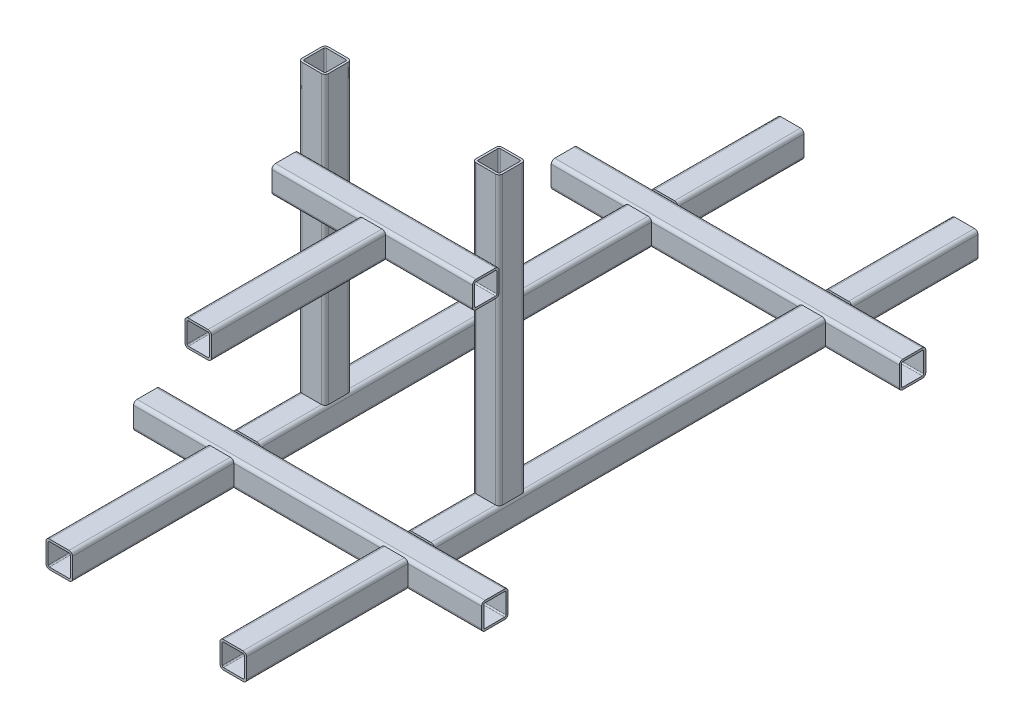
SolidWorks part; units mm, degrees
material "Alumina"
ref_plane "Front Plane" through (0, 0, 0) normal (0, 0, 1) x (1, 0, 0)
ref_plane "Top Plane" through (0, 0, 0) normal (0, 1, 0) x (1, 0, 0)
ref_plane "Right Plane" through (0, 0, 0) normal (1, 0, 0) x (0, 0, -1)
ref_plane "Bottom Face" through (0, 0, 0) normal (0, 1, 0) x (1, 0, 0)
ref_plane "Top Face" through (0, 38.1, 0) normal (0, 1, 0) x (1, 0, 0)
ref_plane "Mid Plane" through (0, 19.05, 0) normal (0, 1, 0) x (1, 0, 0)
ref_plane "Front Face" through (0, 0, 500) normal (0, 0, 1) x (1, 0, 0)
ref_plane "Back Face" through (0, 0, -500) normal (0, 0, 1) x (1, 0, 0)
ref_plane "Left Face" through (250, 0, 0) normal (1, 0, 0) x (0, 0, -1)
ref_plane "Right Face" through (-250, 0, 0) normal (1, 0, 0) x (0, 0, -1)
ref_plane "Divider Plane" through (0, 0, 150) normal (0, 0, 1) x (1, 0, 0)
ref_plane "Max Height Plane" through (0, 450, 0) normal (0, 1, 0) x (1, 0, 0)
ref_plane "Electronics Box Plane" through (0, 338.1, 0) normal (0, 1, 0) x (1, 0, 0)
sketch "Sketch2" plane through (250, 0, 0) normal (1, 0, 0) x (0, 0, -1)
  line L0 (330, 38.1) -> (-330, 38.1) construction
  line L5 (330, 0) -> (-330, 0) construction
  line L6 (0, 220) -> (0, -220) construction
  line L7 (-314.05, 38.1) -> (-285.95, 38.1)
  line L8 (-280.95, 33.1) -> (-280.95, 5)
  line L9 (-315.875, 33.1) -> (-315.875, 5)
  line L10 (-314.05, 3.175) -> (-285.95, 3.175)
  line L11 (-285.95, 0) -> (-314.05, 0)
  line L12 (-319.05, 5) -> (-319.05, 33.1)
  line L13 (-300, 38.1) -> (-300, 0) construction
  line L14 (-319.05, 19.05) -> (-280.95, 19.05) construction
  line L15 (-284.125, 5) -> (-284.125, 33.1)
  line L16 (-285.95, 34.925) -> (-314.05, 34.925)
  line L17 (-300, 34.925) -> (-300, 3.175) construction
  line L18 (-315.875, 19.05) -> (-284.125, 19.05) construction
  arc A0 (-285.95, 38.1) -> (-280.95, 33.1) centre (-285.95, 33.1) cw
  arc A1 (-280.95, 5) -> (-285.95, 0) centre (-285.95, 5) cw
  arc A2 (-314.05, 0) -> (-319.05, 5) centre (-314.05, 5) cw
  arc A3 (-319.05, 33.1) -> (-314.05, 38.1) centre (-314.05, 33.1) cw
  arc A4 (-315.875, 5) -> (-314.05, 3.175) centre (-314.05, 5) ccw
  arc A5 (-285.95, 3.175) -> (-284.125, 5) centre (-285.95, 5) ccw
  arc A6 (-284.125, 33.1) -> (-285.95, 34.925) centre (-285.95, 33.1) ccw
  arc A7 (-314.05, 34.925) -> (-315.875, 33.1) centre (-314.05, 33.1) ccw
  point P20 (-300, 19.05)
  point P39 (-300, 19.05)
  dimension "D1" = 5
  dimension "D2" = 300
  dimension "D3" = 3.175
extrude "Front Cross-Car Member" add sketch "Sketch2" against normal up to surface (500 mm away) up to plane "Right Face"
sketch "Sketch5" plane through (250, 0, 0) normal (1, 0, 0) x (0, 0, -1)
  line L0 (285.95, 38.1) -> (314.05, 38.1)
  line L1 (319.05, 33.1) -> (319.05, 5)
  line L2 (314.05, 0) -> (285.95, 0)
  line L3 (280.95, 5) -> (280.95, 33.1)
  line L4 (300, 38.1) -> (300, 0) construction
  line L5 (280.95, 19.05) -> (319.05, 19.05) construction
  line L6 (285.95, 34.925) -> (314.05, 34.925)
  line L7 (315.875, 33.1) -> (315.875, 5)
  line L8 (314.05, 3.175) -> (285.95, 3.175)
  line L9 (284.125, 5) -> (284.125, 33.1)
  line L10 (300, 34.925) -> (300, 3.175) construction
  line L11 (284.125, 19.05) -> (315.875, 19.05) construction
  line L12 (330, 0) -> (-330, 0) construction
  line L14 (330, 38.1) -> (-330, 38.1) construction
  line L15 (0, 220) -> (0, -220) construction
  arc A0 (314.05, 38.1) -> (319.05, 33.1) centre (314.05, 33.1) cw
  arc A1 (319.05, 5) -> (314.05, 0) centre (314.05, 5) cw
  arc A2 (285.95, 0) -> (280.95, 5) centre (285.95, 5) cw
  arc A3 (280.95, 33.1) -> (285.95, 38.1) centre (285.95, 33.1) cw
  arc A4 (314.05, 34.925) -> (315.875, 33.1) centre (314.05, 33.1) cw
  arc A5 (315.875, 5) -> (314.05, 3.175) centre (314.05, 5) cw
  arc A6 (285.95, 3.175) -> (284.125, 5) centre (285.95, 5) cw
  arc A7 (284.125, 33.1) -> (285.95, 34.925) centre (285.95, 33.1) cw
  point P32 (300, 19.05)
  point P33 (300, 19.05)
  dimension "D2" = 5
  dimension "D1" = 3.175
  dimension "D3" = 300
extrude "Back Cross-Car Member" add sketch "Sketch5" against normal up to surface (500 mm away) separate body up to plane "Right Face"
sketch "Sketch6" plane through (0, 0, -500) normal (0, 0, 1) x (1, 0, 0)
  line L0 (110.95, 38.1) -> (139.05, 38.1)
  line L1 (144.05, 33.1) -> (144.05, 5)
  line L2 (109.125, 33.1) -> (109.125, 5)
  line L3 (110.95, 3.175) -> (139.05, 3.175)
  line L4 (139.05, 0) -> (110.95, 0)
  line L5 (105.95, 5) -> (105.95, 33.1)
  line L6 (125, 38.1) -> (125, 0) construction
  line L7 (105.95, 19.05) -> (144.05, 19.05) construction
  line L8 (140.875, 5) -> (140.875, 33.1)
  line L9 (139.05, 34.925) -> (110.95, 34.925)
  line L10 (125, 34.925) -> (125, 3.175) construction
  line L11 (109.125, 19.05) -> (140.875, 19.05) construction
  line L12 (330, 38.1) -> (-330, 38.1) construction
  line L13 (330, 0) -> (-330, 0) construction
  line L14 (0, -220) -> (0, 220) construction
  arc A0 (139.05, 38.1) -> (144.05, 33.1) centre (139.05, 33.1) cw
  arc A1 (144.05, 5) -> (139.05, 0) centre (139.05, 5) cw
  arc A2 (110.95, 0) -> (105.95, 5) centre (110.95, 5) cw
  arc A3 (105.95, 33.1) -> (110.95, 38.1) centre (110.95, 33.1) cw
  arc A4 (109.125, 5) -> (110.95, 3.175) centre (110.95, 5) ccw
  arc A5 (139.05, 3.175) -> (140.875, 5) centre (139.05, 5) ccw
  arc A6 (140.875, 33.1) -> (139.05, 34.925) centre (139.05, 33.1) ccw
  arc A7 (110.95, 34.925) -> (109.125, 33.1) centre (110.95, 33.1) ccw
  point P16 (125, 19.05)
  point P33 (125, 19.05)
  dimension "D1" = 5
  dimension "D2" = 3.175
  dimension "D3" = 125
extrude "Back Left Along-Car Member" add sketch "Sketch6" along normal blind 180.95
extrude "Middle Left Along-Car Member" add sketch "Sketch6<2>" along normal blind 561.9 from offset 219.05
sketch "Sketch6<2>" plane through (0, 0, -500) normal (0, 0, 1) x (1, 0, 0) same geometry as "Sketch6"
extrude "Front Left Along-Car Member" add sketch "Sketch6<3>" along normal blind 231.75 from offset 819.05
sketch "Sketch6<3>" plane through (0, 0, -500) normal (0, 0, 1) x (1, 0, 0) same geometry as "Sketch6"
sketch "Sketch7" plane through (0, 0, -500) normal (0, 0, 1) x (1, 0, 0)
  line L0 (-139.05, 38.1) -> (-110.95, 38.1)
  line L1 (-105.95, 33.1) -> (-105.95, 5)
  line L2 (-140.875, 33.1) -> (-140.875, 5)
  line L3 (-139.05, 3.175) -> (-110.95, 3.175)
  line L4 (-110.95, 0) -> (-139.05, 0)
  line L5 (-144.05, 5) -> (-144.05, 33.1)
  line L6 (-125, 38.1) -> (-125, 0) construction
  line L7 (-144.05, 19.05) -> (-105.95, 19.05) construction
  line L8 (-109.125, 5) -> (-109.125, 33.1)
  line L9 (-110.95, 34.925) -> (-139.05, 34.925)
  line L10 (-125, 34.925) -> (-125, 3.175) construction
  line L11 (-140.875, 19.05) -> (-109.125, 19.05) construction
  line L12 (330, 38.1) -> (-330, 38.1) construction
  line L13 (330, 0) -> (-330, 0) construction
  line L14 (0, -220) -> (0, 220) construction
  arc A0 (-110.95, 38.1) -> (-105.95, 33.1) centre (-110.95, 33.1) cw
  arc A1 (-105.95, 5) -> (-110.95, 0) centre (-110.95, 5) cw
  arc A2 (-139.05, 0) -> (-144.05, 5) centre (-139.05, 5) cw
  arc A3 (-144.05, 33.1) -> (-139.05, 38.1) centre (-139.05, 33.1) cw
  arc A4 (-140.875, 5) -> (-139.05, 3.175) centre (-139.05, 5) ccw
  arc A5 (-110.95, 3.175) -> (-109.125, 5) centre (-110.95, 5) ccw
  arc A6 (-109.125, 33.1) -> (-110.95, 34.925) centre (-110.95, 33.1) ccw
  arc A7 (-139.05, 34.925) -> (-140.875, 33.1) centre (-139.05, 33.1) ccw
  point P16 (-125, 19.05)
  point P33 (-125, 19.05)
  dimension "D1" = 5
  dimension "D2" = 3.175
  dimension "D3" = 125
extrude "Back Right Along-Car Member" add sketch "Sketch7" along normal blind 180.95
extrude "Middle Right Along-Car Member" add sketch "Sketch7<2>" along normal blind 561.9 from offset 219.05
sketch "Sketch7<2>" plane through (0, 0, -500) normal (0, 0, 1) x (1, 0, 0) same geometry as "Sketch7"
extrude "Front Right Along-Car Member" add sketch "Sketch7<3>" along normal blind 231.75 from offset 819.05
sketch "Sketch7<3>" plane through (0, 0, -500) normal (0, 0, 1) x (1, 0, 0) same geometry as "Sketch7"
sketch "Sketch8" plane through (0, 38.1, 0) normal (0, 1, 0) x (1, 0, 0)
  line L0 (-139.05, -150) -> (-110.95, -150)
  line L1 (-105.95, -155) -> (-105.95, -183.1)
  line L2 (-140.875, -155) -> (-140.875, -183.1)
  line L3 (-139.05, -184.925) -> (-110.95, -184.925)
  line L4 (-110.95, -188.1) -> (-139.05, -188.1)
  line L5 (-144.05, -183.1) -> (-144.05, -155)
  line L6 (-125, -150) -> (-125, -188.1) construction
  line L7 (-144.05, -169.05) -> (-105.95, -169.05) construction
  line L8 (-109.125, -183.1) -> (-109.125, -155)
  line L9 (-110.95, -153.175) -> (-139.05, -153.175)
  line L10 (-125, -153.175) -> (-125, -184.925) construction
  line L11 (-140.875, -169.05) -> (-109.125, -169.05) construction
  line L12 (-220, -150) -> (220, -150) construction
  line L13 (0, -220) -> (0, 220) construction
  arc A0 (-110.95, -150) -> (-105.95, -155) centre (-110.95, -155) cw
  arc A1 (-105.95, -183.1) -> (-110.95, -188.1) centre (-110.95, -183.1) cw
  arc A2 (-139.05, -188.1) -> (-144.05, -183.1) centre (-139.05, -183.1) cw
  arc A3 (-144.05, -155) -> (-139.05, -150) centre (-139.05, -155) cw
  arc A4 (-140.875, -183.1) -> (-139.05, -184.925) centre (-139.05, -183.1) ccw
  arc A5 (-110.95, -184.925) -> (-109.125, -183.1) centre (-110.95, -183.1) ccw
  arc A6 (-109.125, -155) -> (-110.95, -153.175) centre (-110.95, -155) ccw
  arc A7 (-139.05, -153.175) -> (-140.875, -155) centre (-139.05, -155) ccw
  point P16 (-125, -169.05)
  point P33 (-125, -169.05)
  dimension "D1" = 5
  dimension "D2" = 3.175
  dimension "D3" = 38.1
  dimension "D4" = 125
extrude "Right Vertical Member" add sketch "Sketch8" along normal up to surface (411.9 mm away) up to plane "Max Height Plane"
sketch "Sketch10" plane through (0, 38.1, 0) normal (0, 1, 0) x (1, 0, 0)
  line L0 (110.95, -150) -> (139.05, -150)
  line L1 (144.05, -155) -> (144.05, -183.1)
  line L2 (109.125, -155) -> (109.125, -183.1)
  line L3 (110.95, -184.925) -> (139.05, -184.925)
  line L4 (139.05, -188.1) -> (110.95, -188.1)
  line L5 (105.95, -183.1) -> (105.95, -155)
  line L6 (125, -150) -> (125, -188.1) construction
  line L7 (105.95, -169.05) -> (144.05, -169.05) construction
  line L8 (140.875, -183.1) -> (140.875, -155)
  line L9 (139.05, -153.175) -> (110.95, -153.175)
  line L10 (125, -153.175) -> (125, -184.925) construction
  line L11 (109.125, -169.05) -> (140.875, -169.05) construction
  line L12 (-220, -150) -> (220, -150) construction
  line L13 (0, -220) -> (0, 220) construction
  arc A0 (139.05, -150) -> (144.05, -155) centre (139.05, -155) cw
  arc A1 (144.05, -183.1) -> (139.05, -188.1) centre (139.05, -183.1) cw
  arc A2 (110.95, -188.1) -> (105.95, -183.1) centre (110.95, -183.1) cw
  arc A3 (105.95, -155) -> (110.95, -150) centre (110.95, -155) cw
  arc A4 (109.125, -183.1) -> (110.95, -184.925) centre (110.95, -183.1) ccw
  arc A5 (139.05, -184.925) -> (140.875, -183.1) centre (139.05, -183.1) ccw
  arc A6 (140.875, -155) -> (139.05, -153.175) centre (139.05, -155) ccw
  arc A7 (110.95, -153.175) -> (109.125, -155) centre (110.95, -155) ccw
  point P16 (125, -169.05)
  point P33 (125, -169.05)
  dimension "D1" = 5
  dimension "D2" = 3.175
  dimension "D3" = 38.1
  dimension "D4" = 125
extrude "Left Vertical Member" add sketch "Sketch10" along normal up to surface (411.9 mm away) up to plane "Max Height Plane"
sketch "Sketch11" plane through (250, 0, 0) normal (1, 0, 0) x (0, 0, -1)
  line L0 (-221.2, 338.1) -> (-193.1, 338.1)
  line L1 (-188.1, 333.1) -> (-188.1, 305)
  line L2 (-223.025, 333.1) -> (-223.025, 305)
  line L3 (-221.2, 303.175) -> (-193.1, 303.175)
  line L4 (-193.1, 300) -> (-221.2, 300)
  line L5 (-226.2, 305) -> (-226.2, 333.1)
  line L6 (-207.15, 338.1) -> (-207.15, 300) construction
  line L7 (-226.2, 319.05) -> (-188.1, 319.05) construction
  line L8 (-191.275, 305) -> (-191.275, 333.1)
  line L9 (-193.1, 334.925) -> (-221.2, 334.925)
  line L10 (-207.15, 334.925) -> (-207.15, 303.175) construction
  line L11 (-223.025, 319.05) -> (-191.275, 319.05) construction
  line L12 (-150, 220) -> (-150, -220) construction
  line L13 (330, 338.1) -> (-330, 338.1) construction
  arc A0 (-193.1, 338.1) -> (-188.1, 333.1) centre (-193.1, 333.1) cw
  arc A1 (-188.1, 305) -> (-193.1, 300) centre (-193.1, 305) cw
  arc A2 (-221.2, 300) -> (-226.2, 305) centre (-221.2, 305) cw
  arc A3 (-226.2, 333.1) -> (-221.2, 338.1) centre (-221.2, 333.1) cw
  arc A4 (-223.025, 305) -> (-221.2, 303.175) centre (-221.2, 305) ccw
  arc A5 (-193.1, 303.175) -> (-191.275, 305) centre (-193.1, 305) ccw
  arc A6 (-191.275, 333.1) -> (-193.1, 334.925) centre (-193.1, 333.1) ccw
  arc A7 (-221.2, 334.925) -> (-223.025, 333.1) centre (-221.2, 333.1) ccw
  point P16 (-207.15, 319.05)
  point P33 (-207.15, 319.05)
  dimension "D1" = 5
  dimension "D2" = 3.175
  dimension "D3" = 38.1
  dimension "D4" = 38.1
extrude "Upper Cross-Car Member" add sketch "Sketch11" against normal blind 288.1 from offset 105.95 offset against normal yes
sketch "Sketch12" plane through (0, 0, 150) normal (0, 0, 1) x (1, 0, 0)
  line L0 (-14.05, 338.1) -> (14.05, 338.1)
  line L1 (19.05, 333.1) -> (19.05, 305)
  line L2 (-15.875, 333.1) -> (-15.875, 305)
  line L3 (-14.05, 303.175) -> (14.05, 303.175)
  line L4 (14.05, 300) -> (-14.05, 300)
  line L5 (-19.05, 305) -> (-19.05, 333.1)
  line L6 (0, 338.1) -> (0, 300) construction
  line L7 (-19.05, 319.05) -> (19.05, 319.05) construction
  line L8 (15.875, 305) -> (15.875, 333.1)
  line L9 (14.05, 334.925) -> (-14.05, 334.925)
  line L10 (0, 334.925) -> (0, 303.175) construction
  line L11 (-15.875, 319.05) -> (15.875, 319.05) construction
  line L12 (330, 338.1) -> (-330, 338.1) construction
  line L13 (0, -220) -> (0, 220) construction
  arc A0 (14.05, 338.1) -> (19.05, 333.1) centre (14.05, 333.1) cw
  arc A1 (19.05, 305) -> (14.05, 300) centre (14.05, 305) cw
  arc A2 (-14.05, 300) -> (-19.05, 305) centre (-14.05, 305) cw
  arc A3 (-19.05, 333.1) -> (-14.05, 338.1) centre (-14.05, 333.1) cw
  arc A4 (-15.875, 305) -> (-14.05, 303.175) centre (-14.05, 305) ccw
  arc A5 (14.05, 303.175) -> (15.875, 305) centre (14.05, 305) ccw
  arc A6 (15.875, 333.1) -> (14.05, 334.925) centre (14.05, 333.1) ccw
  arc A7 (-14.05, 334.925) -> (-15.875, 333.1) centre (-14.05, 333.1) ccw
  point P16 (0, 319.05)
  point P33 (0, 319.05)
  dimension "D1" = 5
  dimension "D2" = 3.175
  dimension "D3" = 38.1
extrude "E-Box Platform Base" add sketch "Sketch12" along normal blind 250 from offset 76.2
equation "\"D1@Front Face\" = \"frameLength@Master Assembly.SLDASM\" / 2"
equation "\"D1@Back Face\" = \"frameLength@Master Assembly.SLDASM\" / 2"
equation "\"D1@Left Face\"=\"frameWidth@Master Assembly.SLDASM\"/2"
equation "\"D1@Right Face\" = \"frameWidth@Master Assembly.SLDASM\" / 2"
equation "\"D1@Top Face\"=\"frameTubeStockHeight@Master Assembly.SLDASM\""
equation "\"D2@Sketch2\"=\"frameMemberDistLength@Master Assembly.SLDASM\"/2"
equation "\"D3@Sketch2\"=\"frameTubeStockWallThickness@Master Assembly.SLDASM\""
equation "\"D1@Sketch5\"=\"frameTubeStockWallThickness@Master Assembly.SLDASM\""
equation "\"D3@Sketch5\"=\"frameMemberDistLength@Master Assembly.SLDASM\"/2"
equation "\"D3@Sketch6\"=\"frameMemberDistWidth@Master Assembly.SLDASM\"/2"
equation "\"D1@Back Left Along-Car Member\"=(\"frameLength@Master Assembly.SLDASM\" - \"frameMemberDistLength@Master Assembly.SLDASM\" - \"frameTubeStockHeight@Master Assembly.SLDASM\")  / 2"
equation "\"D19@Middle Left Along-Car Member\" = ( \"frameLength@Master Assembly.SLDASM\" - \"frameMemberDistLength@Master Assembly.SLDASM\" + \"frameTubeStockHeight@Master Assembly.SLDASM\" ) / 2"
equation "\"D1@Middle Left Along-Car Member\"=\"frameMemberDistLength@Master Assembly.SLDASM\" - \"frameTubeStockHeight@Master Assembly.SLDASM\""
equation "\"D19@Front Left Along-Car Member\"=( \"frameLength@Master Assembly.SLDASM\" - \"frameMemberDistLength@Master Assembly.SLDASM\" )  / 2 + \"frameMemberDistLength@Master Assembly.SLDASM\" + \"frameTubeStockHeight@Master Assembly.SLDASM\" / 2"
equation "\"D1@Front Left Along-Car Member\" =  ( \"frameLength@Master Assembly.Assembly\" - \"frameMemberDistLength@Master Assembly.Assembly\" - \"frameTubeStockHeight@Master Assembly.Assembly\" )  / 2 + 2in"
equation "\"D3@Sketch7\"=\"frameMemberDistWidth@Master Assembly.SLDASM\"/2"
equation "\"D1@Back Right Along-Car Member\"=(\"frameLength@Master Assembly.SLDASM\" - \"frameMemberDistLength@Master Assembly.SLDASM\" - \"frameTubeStockHeight@Master Assembly.SLDASM\")  / 2"
equation "\"D19@Middle Right Along-Car Member\" = ( \"frameLength@Master Assembly.SLDASM\" - \"frameMemberDistLength@Master Assembly.SLDASM\" + \"frameTubeStockHeight@Master Assembly.SLDASM\" ) / 2"
equation "\"D1@Middle Right Along-Car Member\"=\"frameMemberDistLength@Master Assembly.SLDASM\" - \"frameTubeStockHeight@Master Assembly.SLDASM\""
equation "\"D19@Front Right Along-Car Member\"=( \"frameLength@Master Assembly.SLDASM\" - \"frameMemberDistLength@Master Assembly.SLDASM\" )  / 2 + \"frameMemberDistLength@Master Assembly.SLDASM\" + \"frameTubeStockHeight@Master Assembly.SLDASM\" / 2"
equation "\"D1@Front Right Along-Car Member\"=( \"frameLength@Master Assembly.Assembly\" - \"frameMemberDistLength@Master Assembly.Assembly\" - \"frameTubeStockHeight@Master Assembly.Assembly\" )  / 2 + 2in"
equation "\"D1@Divider Plane\"= \"frameDividerPlaneOffset@Master Assembly.SLDASM\""
equation "\"D3@Sketch8\"=\"frameTubeStockHeight@Master Assembly.SLDASM\""
equation "\"D4@Sketch8\"=\"frameMemberDistWidth@Master Assembly.SLDASM\"/2"
equation "\"D1@Max Height Plane\" = \"frameHeight@Master Assembly.SLDASM\""
equation "\"D4@Sketch10\"=\"frameMemberDistWidth@Master Assembly.SLDASM\"/2"
equation "\"D1@Electronics Box Plane\" = \"eboxPlaneHeight@Master Assembly.SLDASM\""
equation "\"D4@Sketch11\"=\"frameTubeStockHeight@Master Assembly.SLDASM\""
equation "\"D19@Upper Cross-Car Member\" = ( \"frameWidth@Master Assembly.SLDASM\" - \"frameMemberDistWidth@Master Assembly.SLDASM\" - \"frameTubeStockHeight@Master Assembly.SLDASM\" ) / 2"
equation "\"D1@Upper Cross-Car Member\" = \"frameMemberDistWidth@Master Assembly.SLDASM\" + \"frameTubeStockHeight@Master Assembly.SLDASM\""
equation "\"D19@E-Box Platform Base\"= \"frameTubeStockHeight@Master Assembly.SLDASM\" * 2"
equation "\"D2@Sketch6\"=\"frameTubeStockWallThickness@Master Assembly.SLDASM\""
equation "\"D2@Sketch7\"=\"frameTubeStockWallThickness@Master Assembly.SLDASM\""
equation "\"D2@Sketch8\"=\"frameTubeStockWallThickness@Master Assembly.SLDASM\""
equation "\"D3@Sketch10\"=\"frameTubeStockHeight@Master Assembly.SLDASM\""
equation "\"D2@Sketch10\"=\"frameTubeStockWallThickness@Master Assembly.SLDASM\""
equation "\"D3@Sketch11\"=\"frameTubeStockHeight@Master Assembly.SLDASM\""
equation "\"D2@Sketch11\"=\"frameTubeStockWallThickness@Master Assembly.SLDASM\""
equation "\"D3@Sketch12\"=\"frameTubeStockHeight@Master Assembly.SLDASM\""
equation "\"D2@Sketch12\"=\"frameTubeStockWallThickness@Master Assembly.SLDASM\""
